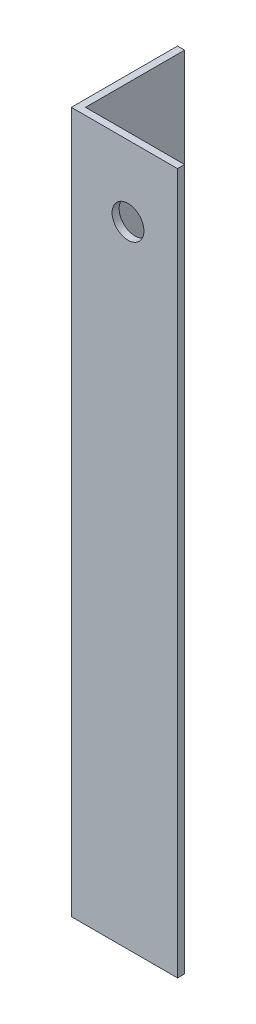
SolidWorks part; units mm, degrees
material "1060 Сплав"
ref_plane "Спереди" through (0, 0, 0) normal (0, 0, 1) x (1, 0, 0)
ref_plane "Сверху" through (0, 0, 0) normal (0, 1, 0) x (1, 0, 0)
ref_plane "Справа" through (0, 0, 0) normal (1, 0, 0) x (0, 0, -1)
sketch "Эскиз1" plane through (0, 0, 0) normal (0, 1, 0) x (1, 0, 0)
  line L0 (0, 0) -> (0, 15)
  line L1 (0, 15) -> (1, 15)
  line L2 (1, 15) -> (1, 1)
  line L3 (1, 1) -> (15, 1)
  line L4 (15, 1) -> (15, 0)
  line L5 (15, 0) -> (0, 0)
  dimension "D1" = 1
  dimension "D2" = 15
extrude "Бобышка-Вытянуть1" add sketch "Эскиз1" along normal blind 99
sketch "Эскиз2" plane through (0, 0, -1) normal (0, 0, -1) x (-1, 0, 0)
  line L0 (-8, 99) -> (-8, 89) construction
  line L1 (-15, 99) -> (-1, 99) construction
  circle A0 centre (-8, 89) radius 2.25
  dimension "D2" = 4.5
  dimension "D1" = 10
extrude "Вырез-Вытянуть1" cut sketch "Эскиз2" against normal through all
